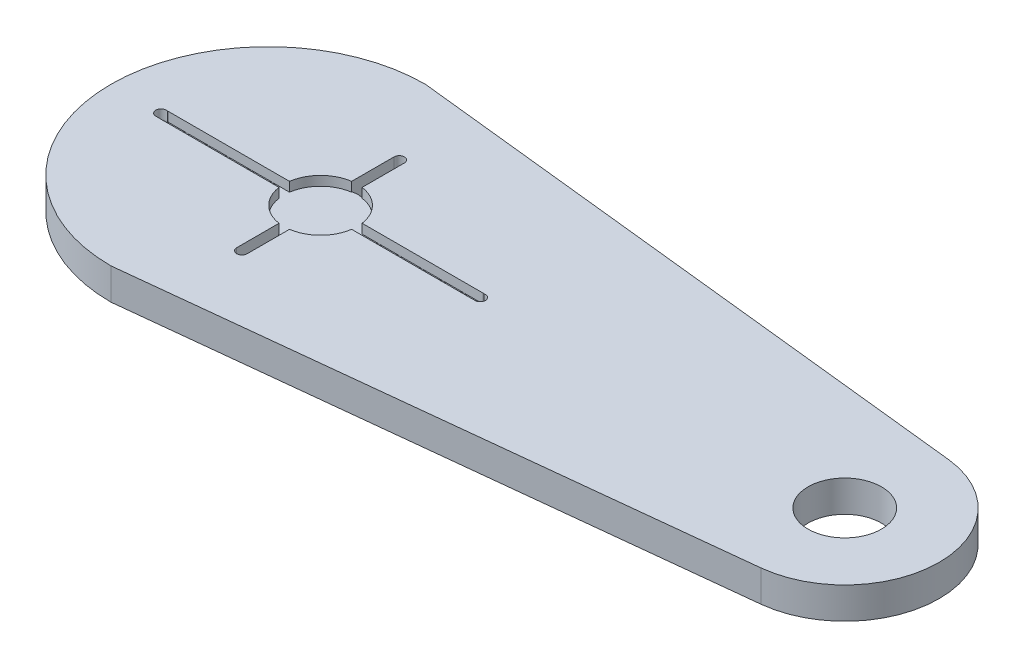
SolidWorks part; units mm, degrees
ref_plane "Front Plane" through (0, 0, 0) normal (0, 0, 1) x (1, 0, 0)
ref_plane "Top Plane" through (0, 0, 0) normal (0, 1, 0) x (1, 0, 0)
ref_plane "Right Plane" through (0, 0, 0) normal (1, 0, 0) x (0, 0, -1)
sketch "Sketch1" plane through (0, 0, 0) normal (0, 1, 0) x (1, 0, 0)
  line L0 (0, -12.7909) -> (0, 17.7714) construction
  line L1 (-20.4064, 0) -> (25.9427, 0) construction
  line L2 (-17.5, -1.95) -> (-17.5, 1.95)
  line L3 (-17.5, 1.95) -> (0, 3.575)
  line L4 (-17.5, -1.95) -> (0, -3.575)
  line L5 (17.5, 1.95) -> (0, 3.575)
  line L6 (17.5, -1.95) -> (17.5, 1.95)
  line L7 (17.5, -1.95) -> (0, -3.575)
  point P10 (-17.5, 0)
  dimension "D1" = 35
  dimension "D2" = 7.15
  dimension "D3" = 3.9
extrude "Boss-Extrude1" add sketch "Sketch1" along normal blind 2.1 contours L3 L5 L6 L7 L4 L2
fillet "Fillet1" 2 edges at (17.5, 1.05, 1.95) (17.5, 1.05, -1.95) type full round first side face at (8.75, 1.05, 2.7625) second side face at (8.75, 1.05, -2.7625) middle face at (17.5, 1.05, 0)
fillet "Fillet2" 2 edges at (-17.5, 1.05, 1.95) (-17.5, 1.05, -1.95) type full round first side face at (-8.75, 1.05, 2.7625) second side face at (-8.75, 1.05, -2.7625) middle face at (-17.5, 1.05, 0)
sketch "Sketch2" plane through (0, 0, 0) normal (0, 1, 0) x (1, 0, 0)
  line L0 (-20.0333, 0) -> (22.2642, 0) construction
  line L1 (0, 11.5337) -> (0, -10.5967) construction
  line L2 (-1.8, -6.35) -> (-1.8, 6.35)
  line L3 (1.8, -6.35) -> (1.8, 6.35)
  arc A0 (-1.8, 6.35) -> (1.8, 6.35) centre (0, 6.35) cw
  arc A1 (-1.8, -6.35) -> (1.8, -6.35) centre (0, -6.35) ccw
  point P5 (0, 8.15)
  point P11 (1.8, 0)
  point P13 (-1.8, 0)
  point P14 (0, -8.15)
  dimension "D2" = 16.3
  dimension "D1" = 3.6
sketch "Sketch3" plane through (0, 2.1, 0) normal (0, 1, 0) x (1, 0, 0)
  circle A0 centre (0, 0) radius 3.4
  dimension "D1" = 6.8
sketch "Sketch5" plane through (0, 0, 0) normal (0, -1, 0) x (1, 0, 0)
  circle A0 centre (0, 0) radius 2.425
  dimension "D1" = 4.85
sketch "Sketch7" plane through (0, 0, 0) normal (0, -1, 0) x (1, 0, 0)
  circle A0 centre (0, 0) radius 2.425
  circle A1 centre (0, 0) radius 3.375
  dimension "D1" = 6.75
extrude "Boss-Extrude4" add sketch "Sketch7" along normal blind 0.5
sketch "Sketch8" plane through (0, 2.1, 0) normal (0, 1, 0) x (1, 0, 0)
  line L0 (0, -11.3552) -> (0, 12.6045) construction
  line L1 (21.3272, 0) -> (-22.6211, 0) construction
  circle A0 centre (0, -6.8539) radius 0.5
  circle A1 centre (0, -4.9129) radius 0.5
  circle A2 centre (-5.0783, 0) radius 0.5
  circle A3 centre (-7.0718, 0) radius 0.5
  circle A4 centre (-9.2663, 0) radius 0.5
  circle A5 centre (-11.1889, 0) radius 0.5
  circle A6 centre (-13.2339, 0) radius 0.5
  circle A7 centre (-15.222, 0) radius 0.5
  circle A8 centre (0, 4.9129) radius 0.5
  circle A9 centre (0, 6.8539) radius 0.5
  circle A10 centre (15.222, 0) radius 0.5
  circle A11 centre (13.2339, 0) radius 0.5
  circle A12 centre (11.1889, 0) radius 0.5
  circle A13 centre (9.2663, 0) radius 0.5
  circle A14 centre (7.0718, 0) radius 0.5
  circle A15 centre (5.0783, 0) radius 0.5
  dimension "D1" = 1
extrude "Cut-Extrude4" cut sketch "Sketch8" against normal through all
sketch "Sketch10" plane through (0, 0, 0) normal (0, 1, 0) x (1, 0, 0)
  line L1 (-20, 15) -> (70, 15)
  line L2 (-20, 15) -> (-20, -15)
  line L3 (-20, -15) -> (70, -15)
  line L4 (70, 15) -> (70, -15)
  circle A0 centre (0, 0) radius 1.15
  circle A1 centre (-9.2663, 0) radius 0.5
  circle A2 centre (-9.2663, 0) radius 0.5
  circle A3 centre (-7.0718, 0) radius 0.5
  circle A4 centre (-7.0718, 0) radius 0.5
  circle A5 centre (-5.0783, 0) radius 0.5
  circle A6 centre (-5.0783, 0) radius 0.5
  circle A7 centre (0, -4.9129) radius 0.5
  circle A8 centre (0, -4.9129) radius 0.5
  circle A9 centre (0, -6.8539) radius 0.5
  circle A10 centre (0, -6.8539) radius 0.5
  circle A11 centre (11.1889, 0) radius 0.5
  circle A12 centre (11.1889, 0) radius 0.5
  circle A13 centre (13.2339, 0) radius 0.5
  circle A14 centre (13.2339, 0) radius 0.5
  circle A15 centre (15.222, 0) radius 0.5
  circle A16 centre (15.222, 0) radius 0.5
  circle A17 centre (0, 6.8539) radius 0.5
  circle A18 centre (0, 6.8539) radius 0.5
  circle A19 centre (0, 4.9129) radius 0.5
  circle A20 centre (0, 4.9129) radius 0.5
  circle A21 centre (-15.222, 0) radius 0.5
  circle A22 centre (-15.222, 0) radius 0.5
  circle A23 centre (-13.2339, 0) radius 0.5
  circle A24 centre (-13.2339, 0) radius 0.5
  circle A25 centre (-11.1889, 0) radius 0.5
  circle A26 centre (-11.1889, 0) radius 0.5
  circle A27 centre (5.0783, 0) radius 0.5
  circle A28 centre (5.0783, 0) radius 0.5
  circle A29 centre (7.0718, 0) radius 0.5
  circle A30 centre (7.0718, 0) radius 0.5
  circle A31 centre (9.2663, 0) radius 0.5
  circle A32 centre (9.2663, 0) radius 0.5
  circle A33 centre (50, 0) radius 3
  point P58 (-20, 0)
  dimension "D19" = 50
  dimension "D17" = 90
  dimension "D18" = 20
  dimension "D20" = 30
  dimension "D1" = 0
  dimension "D2" = 0
  dimension "D3" = 0
  dimension "D4" = 0
  dimension "D5" = 0
  dimension "D6" = 0
  dimension "D7" = 0
  dimension "D8" = 0
  dimension "D9" = 0
  dimension "D10" = 0
  dimension "D11" = 0
  dimension "D12" = 0
  dimension "D13" = 0
  dimension "D14" = 0
  dimension "D15" = 0
  dimension "D16" = 0
extrude "Boss-Extrude5" add sketch "Sketch10" along normal blind 3 separate body
sketch "Sketch11" plane through (0, 0, 0) normal (0, 1, 0) x (1, 0, 0)
  circle A0 centre (50, 0) radius 3 construction
  circle A1 centre (50, 0) radius 3
  dimension "D1" = 6
extrude "Boss-Extrude6" add sketch "Sketch11" along normal blind 20
sketch "Sketch12" plane through (0, 3, 0) normal (0, 1, 0) x (1, 0, 0)
  circle A1 centre (0, 0) radius 3.375
  circle A2 centre (0, 0) radius 3.375
  dimension "D2" = 6.75
  dimension "D1" = 0
extrude "Cut-Extrude10" cut sketch "Sketch12" against normal blind 20
fillet "Fillet4" 2 edges at (-20, 1.5, -15) (-20, 1.5, 15) type full round first side face at (25, 1.5, -15) second side face at (25, 1.5, 15) middle face at (-20, 1.5, 0)
sketch "Sketch16" plane through (0, 3, 0) normal (0, 1, 0) x (1, 0, 0)
  line L0 (50.9676, 8.9478) -> (-5, 15)
  line L1 (-5, 15) -> (76.9551, 20.3699)
  line L2 (76.9551, 20.3699) -> (78.9681, -25.2586)
  line L3 (78.9681, -25.2586) -> (-5, -15)
  line L4 (-5, -15) -> (50.9676, -8.9478)
  circle A0 centre (50, 0) radius 9
  line M11 (-5, -15) -> (70, -15)
  line M12 (70, -15) -> (70, 15)
  line M13 (70, 15) -> (-5, 15)
  dimension "D1" = 18
extrude "Cut-Extrude12" cut sketch "Sketch16" against normal through all contours A0 L4 L0 M11 M12 M13 | L3 L2 L1 M13 M12 M11 region at (23.0706, 3, -12.777) region at (36.04, 3, -16.7313)
sketch "Sketch17" plane through (0, 3, 0) normal (0, 1, 0) x (1, 0, 0)
  line L0 (-15, 0) -> (15, 0) construction
  line L1 (-15, 0.5) -> (15, 0.5)
  line L2 (-15, -0.5) -> (15, -0.5)
  line L3 (0, -7.5) -> (0, 7.5) construction
  line L4 (-0.5, -7.5) -> (-0.5, 7.5)
  line L5 (0.5, -7.5) -> (0.5, 7.5)
  arc A0 (-15, 0.5) -> (-15, -0.5) centre (-15, 0) ccw
  arc A1 (15, -0.5) -> (15, 0.5) centre (15, 0) ccw
  arc A3 (-0.5, -7.5) -> (0.5, -7.5) centre (0, -7.5) ccw
  arc A4 (0.5, 7.5) -> (-0.5, 7.5) centre (0, 7.5) ccw
  point P2 (0, 0)
  point P10 (0, 0)
  dimension "D1" = 0.5
  dimension "D2" = 0.5
  dimension "D3" = 15
  dimension "D4" = 30
  dimension "D5" = 30
extrude "Cut-Extrude13" cut sketch "Sketch17" against normal through all contours L2 A1 L1 A0 | L4 A4 L5 A3
sketch "Sketch18" plane through (0, 3, 0) normal (0, 1, 0) x (1, 0, 0)
  circle A0 centre (0, 0) radius 3.5
extrude "Cut-Extrude14" cut sketch "Sketch18" against normal blind 10
sketch "Sketch19" plane through (0, 20, 0) normal (0, 1, 0) x (1, 0, 0)
  circle A0 centre (50, 0) radius 3.5
  dimension "D1" = 7
extrude "Boss-Extrude7" add sketch "Sketch19" against normal up to surface (17 mm away) and the other way blind 10 up to face at (0, 3, 0)
sketch "Sketch21" plane through (0, 30, 0) normal (0, 1, 0) x (1, 0, 0)
  circle A0 centre (50, 0) radius 3.5
extrude "Cut-Extrude16" cut sketch "Sketch21" against normal through all both
